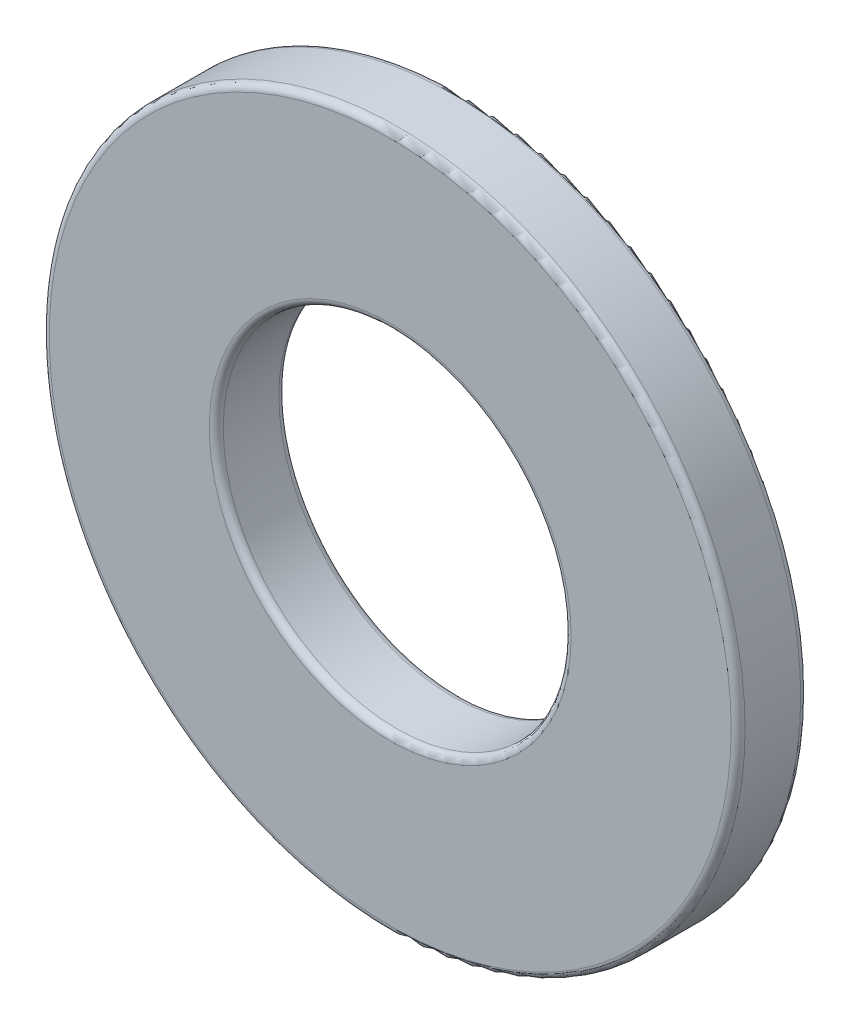
SolidWorks part; units mm, degrees
ref_plane "Front Plane" through (0, 0, 0) normal (0, 0, 1) x (1, 0, 0)
ref_plane "Top Plane" through (0, 0, 0) normal (0, 1, 0) x (1, 0, 0)
ref_plane "Right Plane" through (0, 0, 0) normal (1, 0, 0) x (0, 0, -1)
sketch "Sketch1" plane through (0, 0, 0) normal (0, 0, 1) x (1, 0, 0)
  line L0 (-15.875, 0) -> (-7.9375, 0) construction
  line L1 (-7.9375, 0) -> (7.9375, 0) construction
  line L2 (7.9375, 0) -> (15.875, 0) construction
  line L3 (0, 15.875) -> (0, -15.875) construction
  circle A0 centre (0, 0) radius 7.9375 construction
  circle A1 centre (0, 0) radius 15.875 construction
  point P11 (7.9375, 0)
  point P12 (-7.9375, 0)
  dimension "ID" = 15.875
  dimension "OD" = 31.75
sketch "Sketch2" plane through (0, 0, 0) normal (1, 0, 0) x (0, 0, -1)
  line L1 (-1.5875, -15.875) -> (1.5875, -15.875) construction
  line L2 (-1.5875, -15.875) -> (-1.5875, 15.875) construction
  line L3 (-1.5875, 15.875) -> (1.5875, 15.875) construction
  line L4 (1.5875, -15.875) -> (1.5875, 15.875) construction
  line L5 (-1.5875, -15.875) -> (1.5875, 15.875) construction
  line L6 (-1.5875, 15.875) -> (1.5875, -15.875) construction
  point P0 (0, 0)
  dimension "Thickness" = 3.175
sketch "Sketch3" plane through (0, 0, 0) normal (0, 0, 1) x (1, 0, 0)
  circle A0 centre (0, 0) radius 7.9375 construction
  circle A1 centre (0, 0) radius 15.875 construction
  circle A2 centre (0, 0) radius 7.9375
  circle A3 centre (0, 0) radius 15.875
extrude "Boss-Extrude1" add sketch "Sketch3" along normal up to vertex (1.5875 mm away) and the other way up to vertex (1.5875 mm away) up to point (0, 15.875, 1.5875) other way up to point (0, 15.875, -1.5875)
fillet "Fillet1" radius 0.3175 4 edges at (15.875, 0, -1.5875) (7.9375, 0, -1.5875) (7.9375, 0, 1.5875) (15.875, 0, 1.5875)
equation "\"D1@Fillet1\"=\"Thickness@Sketch2\"*.1"
